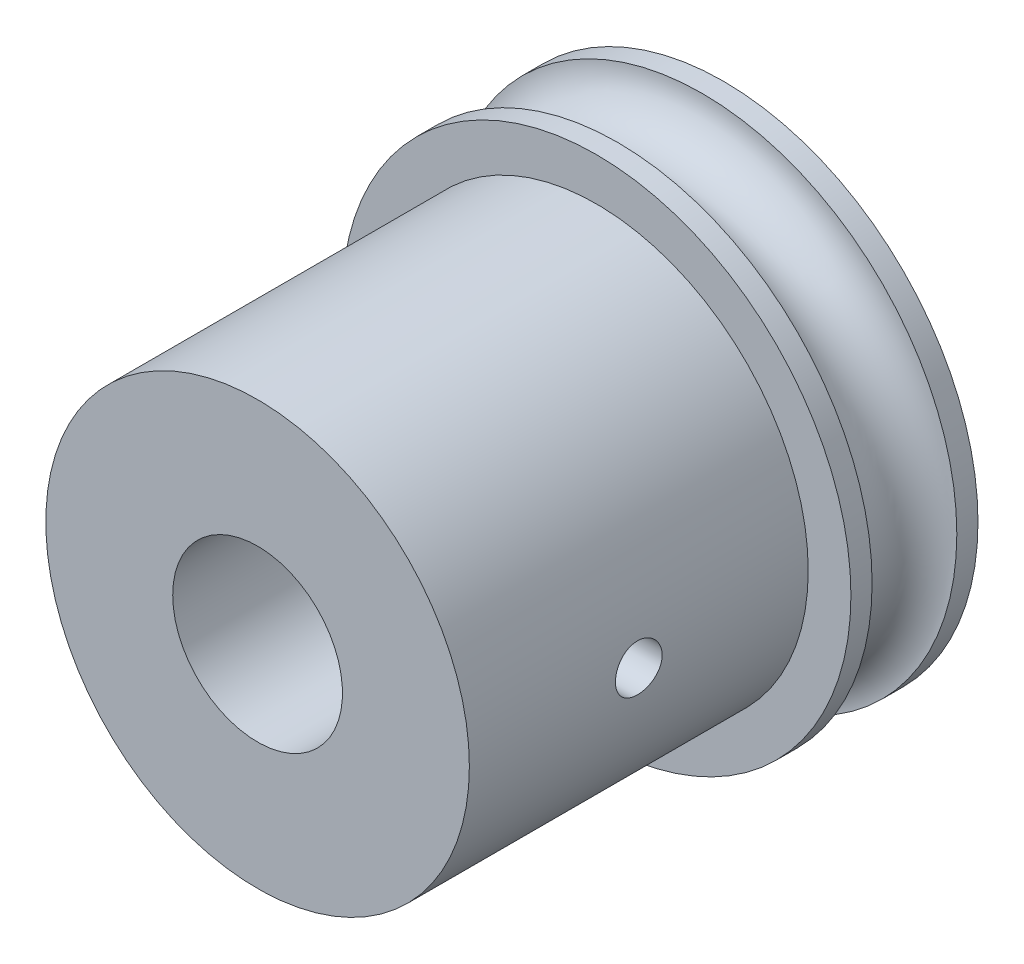
SolidWorks part; units mm, degrees
ref_plane "Front Plane" through (0, 0, 0) normal (0, 0, 1) x (1, 0, 0)
ref_plane "Top Plane" through (0, 0, 0) normal (0, 1, 0) x (1, 0, 0)
ref_plane "Right Plane" through (0, 0, 0) normal (1, 0, 0) x (0, 0, -1)
sketch "Sketch1" plane through (0, 0, 0) normal (0, 1, 0) x (1, 0, 0)
  line L0 (9.5377, 2.3812) -> (0, 2.3812)
  line L1 (0, 2.3812) -> (0, -2.3812)
  line L2 (0, -2.3812) -> (9.5377, -2.3812)
  line L3 (9.5377, -2.3812) -> (9.5377, -1.5875)
  line L4 (9.5377, 1.5875) -> (9.5377, 2.3812)
  line L5 (0, 2.3812) -> (0, -2.3812) construction
  arc A0 (9.5377, -1.5875) -> (9.5377, 1.5875) centre (9.5377, 0) cw
revolve "Revolve1" add sketch "Sketch1" angle 360 about L5 reverse direction yes
sketch "Sketch2" plane through (0, 0, 2.3812) normal (0, 0, 1) x (1, 0, 0)
  circle A0 centre (0, 0) radius 7.9375
extrude "Boss-Extrude1" add sketch "Sketch2" along normal blind 12.7
hole_wizard "Hole1" positions "Sketch4" profile "Sketch3" legacy
sketch "Sketch4" plane through (0, 0, -2.3812) normal (0, 0, -1) x (-1, 0, 0)
  point P0 (0, 0)
sketch "Sketch3" plane through (0, 0, -2.3812) normal (1, 0, 0) x (0, 1, 0)
  line L0 (0, 0) -> (0, 17.4625)
  line L1 (0, 17.4625) -> (3.1814, 17.4625)
  line L2 (3.1814, 17.4625) -> (3.1814, 0)
  line L3 (3.1814, 0) -> (0, 0)
  line L4 (0, 110) -> (0, -10) construction
  dimension "Diameter" = 6.3627
  dimension "Depth" = 17.4625
ref_plane "Plane1" through (3.0583, 0, 0) normal (-1, 0, 0) x (0, 0, 1)
hole_wizard "M1.6 Clearance Hole1" positions "Sketch6" profile "Sketch5" hole size "M1.6" standard "ANSI Metric"
sketch "Sketch6" plane through (3.0583, 0, 0) normal (-1, 0, 0) x (0, 0, 1)
  point P0 (8.7312, 0)
sketch "Sketch5" plane through (3.0583, 0, 8.7312) normal (0, 1, 0) x (0, 0, 1)
  line L0 (0, 0) -> (0, 6.4794)
  line L1 (0, 6.4794) -> (0.8763, 6.4794)
  line L2 (0.8763, 6.4794) -> (0.8763, 0)
  line L5 (0.8763, 0) -> (0, 0)
  line L11 (0, -6.35) -> (0, 107.95) construction
  dimension "Thru Hole Dia." = 1.7526
  dimension "Thru Hole Depth" = 6.4794
ref_axis "Axis1" through (7.9375, 0, 8.7312) along (-1, 0, 0)
